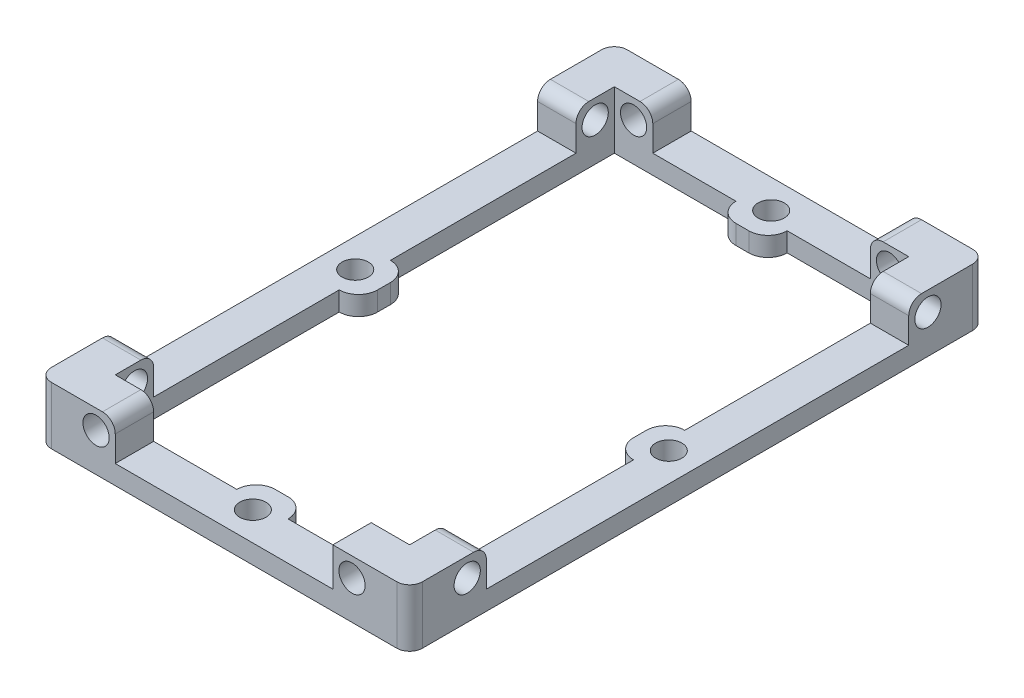
SolidWorks part; units mm, degrees
material "ABS"
ref_plane "Front Plane" through (0, 0, 0) normal (0, 0, 1) x (1, 0, 0)
ref_plane "Top Plane" through (0, 0, 0) normal (0, 1, 0) x (1, 0, 0)
ref_plane "Right Plane" through (0, 0, 0) normal (1, 0, 0) x (0, 0, -1)
sketch "Sketch1" plane through (0, 0, 0) normal (0, 1, 0) x (1, 0, 0)
  line L0 (6, -6) -> (52, -6)
  line L1 (0, 0) -> (58, 0)
  line L2 (0, 0) -> (0, -90)
  line L3 (0, -90) -> (58, -90)
  line L4 (58, 0) -> (58, -90)
  line L5 (52, -6) -> (52, -84)
  line L6 (6, -84) -> (52, -84)
  line L7 (6, -6) -> (6, -84)
  dimension "D1" = 90
  dimension "D2" = 58
  dimension "D3" = 6
extrude "Boss-Extrude1" add sketch "Sketch1" along normal blind 3
sketch "Sketch2" plane through (0, 3, 0) normal (0, 1, 0) x (1, 0, 0)
  line L0 (46, -90) -> (46, -84)
  line L1 (0, -90) -> (58, -90) construction
  line L2 (6, -84) -> (52, -84) construction
  line L3 (52, -78) -> (58, -78)
  line L4 (52, -84) -> (52, -6) construction
  line L5 (58, -90) -> (58, 0) construction
  line L6 (46, -84) -> (52, -84)
  line L7 (46, -90) -> (58, -90)
  line L8 (58, -90) -> (58, -78)
  line L9 (52, -84) -> (52, -78)
  line L10 (0, -45) -> (58, -45) construction
  line L11 (0, 0) -> (0, -90) construction
  line L12 (29, 0) -> (29, -90) construction
  line L13 (58, 0) -> (0, 0) construction
  line L14 (46, 0) -> (46, -6)
  line L15 (46, 0) -> (58, 0)
  line L16 (58, 0) -> (58, -12)
  line L17 (52, -12) -> (58, -12)
  line L18 (52, -6) -> (52, -12)
  line L19 (46, -6) -> (52, -6)
  line L20 (12, -90) -> (12, -84)
  line L21 (12, -90) -> (0, -90)
  line L22 (0, -90) -> (0, -78)
  line L23 (6, -78) -> (0, -78)
  line L24 (6, -84) -> (6, -78)
  line L25 (12, -84) -> (6, -84)
  line L26 (12, -6) -> (6, -6)
  line L27 (12, 0) -> (12, -6)
  line L28 (12, 0) -> (0, 0)
  line L29 (0, 0) -> (0, -12)
  line L30 (6, -12) -> (0, -12)
  line L31 (6, -6) -> (6, -12)
  line M3 (0, 0) -> (0, -90)
  line M4 (0, -90) -> (58, -90)
  line M5 (58, -90) -> (58, 0)
  line M6 (58, 0) -> (0, 0)
  line M7 (52, -84) -> (6, -84)
  line M8 (6, -84) -> (6, -6)
  line M9 (6, -6) -> (52, -6)
  line M10 (52, -6) -> (52, -84)
  dimension "D1" = 6
  dimension "D2" = 6
extrude "Boss-Extrude2" add sketch "Sketch2" along normal blind 6 contours L3 L0 M10 M7 M4 M5 | L17 L14 M10 M5 M6 M9 | L30 L27 M8 M9 M6 M3 | L23 L20 M8 M3 M4 M7 region at (53, 3, 85) region at (5, 3, 85) region at (53, 3, 5) region at (5, 3, 5)
sketch "Sketch3" plane through (0, 0, 0) normal (-1, 0, 0) x (0, 0, 1)
  line L0 (12, 9) -> (6, 9) construction
  line L1 (12, 9) -> (6, 9)
  line L2 (9, 9) -> (9, 3) construction
  line L3 (45, 0) -> (45, 3) construction
  line L8 (0, 0) -> (90, 0)
  line L9 (90, 0) -> (90, 9)
  line L10 (90, 9) -> (78, 9)
  line L11 (78, 9) -> (78, 3)
  line L12 (78, 3) -> (12, 3)
  line L13 (12, 3) -> (12, 9)
  line L14 (12, 9) -> (0, 9)
  line L15 (0, 9) -> (0, 0)
  line L16 (0, 0) -> (90, 0)
  line L17 (90, 0) -> (90, 9)
  line L18 (90, 9) -> (78, 9)
  line L19 (78, 9) -> (78, 3)
  line L20 (78, 3) -> (12, 3)
  line L21 (12, 3) -> (12, 9)
  line L22 (12, 9) -> (0, 9)
  line L23 (0, 9) -> (0, 0)
  circle A0 centre (9, 6) radius 2.05
  circle A1 centre (81, 6) radius 2.05
  dimension "D2" = 4.1
  dimension "D1" = 0
extrude "Cut-Extrude1" cut sketch "Sketch3" against normal through all contours A0 | A1 region at (0, 6, 9) region at (0, 6, 81)
sketch "Sketch4" plane through (0, 0, 0) normal (0, 0, -1) x (-1, 0, 0)
  line L0 (-46, 9) -> (-52, 9) construction
  line L1 (-46, 9) -> (-52, 9)
  line L2 (-46, 9) -> (-46, 3) construction
  line L3 (-46, 9) -> (-46, 3)
  line L4 (-49, 9) -> (-49, 3) construction
  line L5 (-46, 3) -> (-12, 3) construction
  line L6 (-46, 3) -> (-12, 3)
  line L7 (-29, 3) -> (-29, 0) construction
  line L8 (-58, 0) -> (0, 0) construction
  circle A0 centre (-49, 6) radius 2.05
  circle A1 centre (-9, 6) radius 2.05
  dimension "D1" = 4.1
extrude "Cut-Extrude2" cut sketch "Sketch4" against normal through all contours A0 | A1 region at (49, 6, 0) region at (9, 6, 0)
fillet "Fillet1" radius 2 7 edges at (3, 9, 12) (12, 9, 87) (3, 9, 78) (12, 9, 3) (46, 9, 3) (55, 9, 12) (55, 9, 78)
fillet "Fillet2" radius 2 4 edges at (0, 4.5, 90) (58, 4.5, 90) (0, 4.5, 0) (58, 4.5, 0)
sketch "Sketch5" plane through (0, 0, 0) normal (0, -1, 0) x (1, 0, 0)
  line L13 (6, 84) -> (52, 84) construction
  line L14 (33, 84) -> (25, 84)
  line L15 (33, 84) -> (33, 81)
  line L16 (33, 81) -> (25, 81)
  line L17 (25, 84) -> (25, 81)
  line L18 (52, 6) -> (6, 6) construction
  line L19 (33, 6) -> (25, 6)
  line L20 (33, 6) -> (33, 9)
  line L21 (33, 9) -> (25, 9)
  line L22 (25, 6) -> (25, 9)
  line L23 (56, 0) -> (2, 0) construction
  line L24 (56, 0) -> (2, 0)
  point P14 (29, 9)
  point P15 (29, 0)
  point P16 (29, 81)
  line M23 (6, 84) -> (52, 84)
  line M25 (52, 6) -> (6, 6)
  dimension "D1" = 8
  dimension "D2" = 8
  dimension "D3" = 3
  dimension "D4" = 3
extrude "Boss-Extrude3" add sketch "Sketch5" against normal up to surface (3 mm away) contours L22 L20 L21 M25 | L17 L16 L15 M23 region at (29, 0, 82.5) region at (29, 0, 7.5) up to face at (29, 3, 87)
sketch "Sketch6" plane through (0, 0, 0) normal (0, -1, 0) x (1, 0, 0)
  line L0 (33, 9) -> (25, 9) construction
  line L1 (33, 81) -> (25, 81) construction
  line L2 (33, 9) -> (25, 9)
  line L3 (33, 81) -> (25, 81)
  line L4 (29, 81) -> (29, 90) construction
  line L5 (2, 90) -> (56, 90) construction
  line L6 (29, 9) -> (29, 0) construction
  line L7 (56, 0) -> (2, 0) construction
  circle A0 centre (29, 85.5) radius 2.05
  circle A1 centre (29, 4.5) radius 2.05
  dimension "D1" = 4.1
  dimension "D2" = 4.1
extrude "Cut-Extrude3" cut sketch "Sketch6" along direction (0, 1, 0) on the side against the normal up to surface (3 mm away) contours A0 | A1 region at (29, 0, 85.5) region at (29, 0, 4.5) up to face at (3, 3, 45)
fillet "Fillet3" radius 3 4 edges at (33, 1.5, 81) (25, 1.5, 81) (33, 1.5, 9) (25, 1.5, 9)
sketch "Sketch7" plane through (0, 0, 0) normal (0, -1, 0) x (1, 0, 0)
  line L0 (52, 45) -> (49, 45) construction
  line L1 (52, 84) -> (52, 6) construction
  line L2 (6, 6) -> (6, 84) construction
  line L3 (52, 49) -> (49, 49)
  line L4 (52, 41) -> (49, 41)
  line L5 (49, 41) -> (49, 49)
  line L6 (9, 41) -> (9, 49)
  line L7 (9, 45) -> (6, 45) construction
  line L8 (52, 45) -> (6, 45) construction
  line L9 (9, 49) -> (6, 49)
  line L10 (52, 49) -> (6, 49) construction
  line L11 (9, 41) -> (6, 41)
  line L12 (52, 41) -> (6, 41) construction
  line L13 (6, 41) -> (6, 49)
  line L14 (52, 41) -> (52, 49)
  dimension "D3" = 3
  dimension "D4" = 3
  dimension "D1" = 4
  dimension "D2" = 4
extrude "Boss-Extrude4" add sketch "Sketch7" against normal up to surface (3 mm away) up to face at (3, 3, 45)
sketch "Sketch8" plane through (0, 3, 0) normal (0, 1, 0) x (1, 0, 0)
  line L0 (0, -45) -> (9, -45) construction
  line L1 (0, -12) -> (0, -78) construction
  line L2 (9, -41) -> (9, -49) construction
  line L3 (49, -45) -> (58, -45) construction
  line L5 (49, -49) -> (49, -41) construction
  line L6 (58, -78) -> (58, -12) construction
  circle A0 centre (4.5, -45) radius 2.05
  circle A1 centre (53.5, -45) radius 2.05
  dimension "D1" = 4.1
  dimension "D2" = 4.1
extrude "Cut-Extrude4" cut sketch "Sketch8" against normal through all
fillet "Fillet4" radius 3 4 edges at (49, 1.5, 41) (49, 1.5, 49) (9, 1.5, 41) (9, 1.5, 49)
equation "\"Depth\"= 90mm"
equation "\"Height\" = 150mm"
equation "\"Width\"= 64mm"
equation "\"D1@Sketch1\"=\"Depth\""
equation "\"D2@Sketch1\"=\"Width\"-6"
equation "\"4mmPLA\"=4.1"
equation "\"D1@Sketch4\"=\"4mmPLA\""
equation "\"D1@Sketch6\"=\"4mmPLA\""
equation "\"D2@Sketch6\"=\"4mmPLA\""
equation "\"D1@Sketch8\"=\"4mmPLA\""
equation "\"D2@Sketch8\"=\"4mmPLA\""
